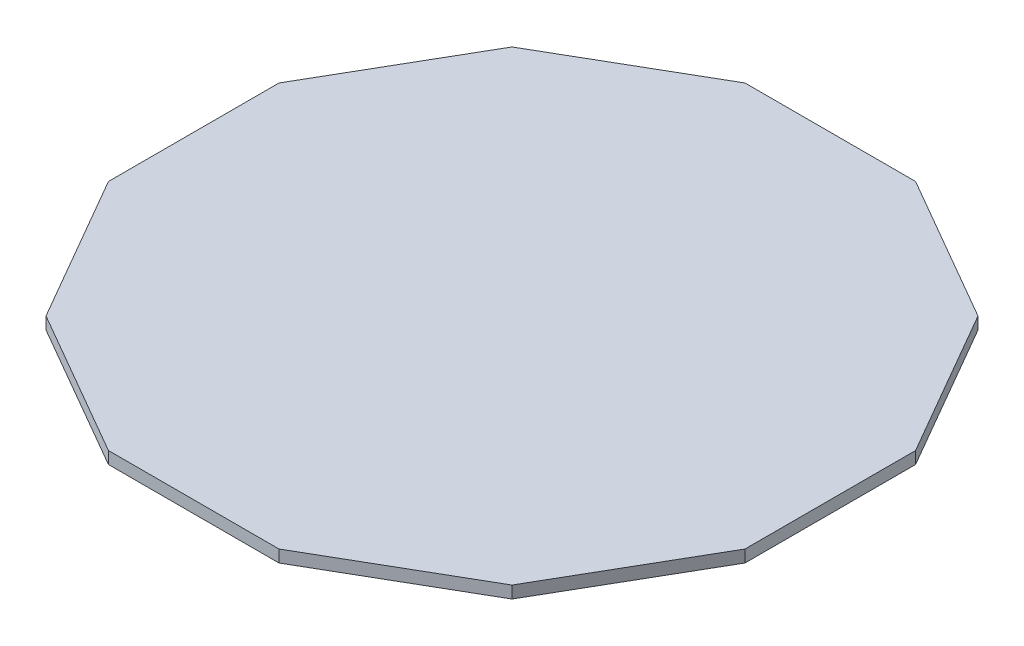
SolidWorks part; units mm, degrees
material "ABS PC"
ref_plane "Front Plane" through (0, 0, 0) normal (0, 0, 1) x (1, 0, 0)
ref_plane "Top Plane" through (0, 0, 0) normal (0, 1, 0) x (1, 0, 0)
ref_plane "Right Plane" through (0, 0, 0) normal (1, 0, 0) x (0, 0, -1)
sketch "Sketch1" plane through (0, 0, 0) normal (0, 1, 0) x (1, 0, 0)
  line L0 (19.722, 73.6035) -> (-19.722, 73.6035)
  line L1 (-19.722, 73.6035) -> (-53.8815, 53.8815)
  line L2 (-53.8815, 53.8815) -> (-73.6035, 19.722)
  line L3 (-73.6035, 19.722) -> (-73.6035, -19.722)
  line L4 (-73.6035, -19.722) -> (-53.8815, -53.8815)
  line L5 (-53.8815, -53.8815) -> (-19.722, -73.6035)
  line L6 (-19.722, -73.6035) -> (19.722, -73.6035)
  line L7 (19.722, -73.6035) -> (53.8815, -53.8815)
  line L8 (53.8815, -53.8815) -> (73.6035, -19.722)
  line L9 (73.6035, -19.722) -> (73.6035, 19.722)
  line L10 (73.6035, 19.722) -> (53.8815, 53.8815)
  line L11 (53.8815, 53.8815) -> (19.722, 73.6035)
  circle A0 centre (0, 0) radius 76.2
  dimension "D1" = 152.4
extrude "Boss-Extrude1" add sketch "Sketch1" against normal blind 2.921 contours L10 L11 L0 L1 L2 L3 L4 L5 L6 L7 L8 L9 region at (0, 0, 0)
sketch "Sketch2" plane through (0, 0, 0) normal (0, 1, 0) x (1, 0, 0)
  line L24 (76.5245, 20.5047) -> (56.0199, 56.0199)
  line L25 (56.0199, 56.0199) -> (20.5047, 76.5245)
  line L26 (20.5047, 76.5245) -> (-20.5047, 76.5245)
  line L27 (-20.5047, 76.5245) -> (-56.0199, 56.0199)
  line L28 (-56.0199, 56.0199) -> (-76.5245, 20.5047)
  line L29 (-76.5245, 20.5047) -> (-76.5245, -20.5047)
  line L30 (-76.5245, -20.5047) -> (-56.0199, -56.0199)
  line L31 (-56.0199, -56.0199) -> (-20.5047, -76.5245)
  line L32 (-20.5047, -76.5245) -> (20.5047, -76.5245)
  line L33 (20.5047, -76.5245) -> (56.0199, -56.0199)
  line L34 (56.0199, -56.0199) -> (76.5245, -20.5047)
  line L35 (76.5245, -20.5047) -> (76.5245, 20.5047)
  line L36 (76.5245, 20.5047) -> (56.0199, 56.0199)
  line L37 (56.0199, 56.0199) -> (20.5047, 76.5245)
  line L38 (20.5047, 76.5245) -> (-20.5047, 76.5245)
  line L39 (-20.5047, 76.5245) -> (-56.0199, 56.0199)
  line L40 (-56.0199, 56.0199) -> (-76.5245, 20.5047)
  line L41 (-76.5245, 20.5047) -> (-76.5245, -20.5047)
  line L42 (-76.5245, -20.5047) -> (-56.0199, -56.0199)
  line L43 (-56.0199, -56.0199) -> (-20.5047, -76.5245)
  line L44 (-20.5047, -76.5245) -> (20.5047, -76.5245)
  line L45 (20.5047, -76.5245) -> (56.0199, -56.0199)
  line L46 (56.0199, -56.0199) -> (76.5245, -20.5047)
  line L47 (76.5245, -20.5047) -> (76.5245, 20.5047)
  line L60 (73.6035, 19.722) -> (53.8815, 53.8815)
  line L61 (53.8815, 53.8815) -> (19.722, 73.6035)
  line L62 (19.722, 73.6035) -> (-19.722, 73.6035)
  line L63 (-19.722, 73.6035) -> (-53.8815, 53.8815)
  line L64 (-53.8815, 53.8815) -> (-73.6035, 19.722)
  line L65 (-73.6035, 19.722) -> (-73.6035, -19.722)
  line L66 (-73.6035, -19.722) -> (-53.8815, -53.8815)
  line L67 (-53.8815, -53.8815) -> (-19.722, -73.6035)
  line L68 (-19.722, -73.6035) -> (19.722, -73.6035)
  line L69 (19.722, -73.6035) -> (53.8815, -53.8815)
  line L70 (53.8815, -53.8815) -> (73.6035, -19.722)
  line L71 (73.6035, -19.722) -> (73.6035, 19.722)
  line L72 (73.6035, 19.722) -> (53.8815, 53.8815)
  line L73 (53.8815, 53.8815) -> (19.722, 73.6035)
  line L74 (19.722, 73.6035) -> (-19.722, 73.6035)
  line L75 (-19.722, 73.6035) -> (-53.8815, 53.8815)
  line L76 (-53.8815, 53.8815) -> (-73.6035, 19.722)
  line L77 (-73.6035, 19.722) -> (-73.6035, -19.722)
  line L78 (-73.6035, -19.722) -> (-53.8815, -53.8815)
  line L79 (-53.8815, -53.8815) -> (-19.722, -73.6035)
  line L80 (-19.722, -73.6035) -> (19.722, -73.6035)
  line L81 (19.722, -73.6035) -> (53.8815, -53.8815)
  line L82 (53.8815, -53.8815) -> (73.6035, -19.722)
  line L83 (73.6035, -19.722) -> (73.6035, 19.722)
  circle A0 centre (0, 0) radius 79.224
  line M13 (73.6035, 19.722) -> (53.8815, 53.8815)
  line M14 (53.8815, 53.8815) -> (19.722, 73.6035)
  line M15 (19.722, 73.6035) -> (-19.722, 73.6035)
  line M16 (-19.722, 73.6035) -> (-53.8815, 53.8815)
  line M17 (-53.8815, 53.8815) -> (-73.6035, 19.722)
  line M18 (-73.6035, 19.722) -> (-73.6035, -19.722)
  line M19 (-73.6035, -19.722) -> (-53.8815, -53.8815)
  line M20 (-53.8815, -53.8815) -> (-19.722, -73.6035)
  line M21 (-19.722, -73.6035) -> (19.722, -73.6035)
  line M22 (19.722, -73.6035) -> (53.8815, -53.8815)
  line M23 (53.8815, -53.8815) -> (73.6035, -19.722)
  line M24 (73.6035, -19.722) -> (73.6035, 19.722)
  dimension "D1" = 2.921
  dimension "D2" = 0
extrude "Boss-Extrude2" add sketch "Sketch2" against normal up to surface (2.921 mm away) contours L46 L47 L36 L37 L38 L39 L40 L41 L42 L43 L44 L45 M13 M24 M23 M22 M21 M20 M19 M18 M17 M16 M15 M14 region at (74.3601, 0, 0) up to face at (0, -2.921, 0)
